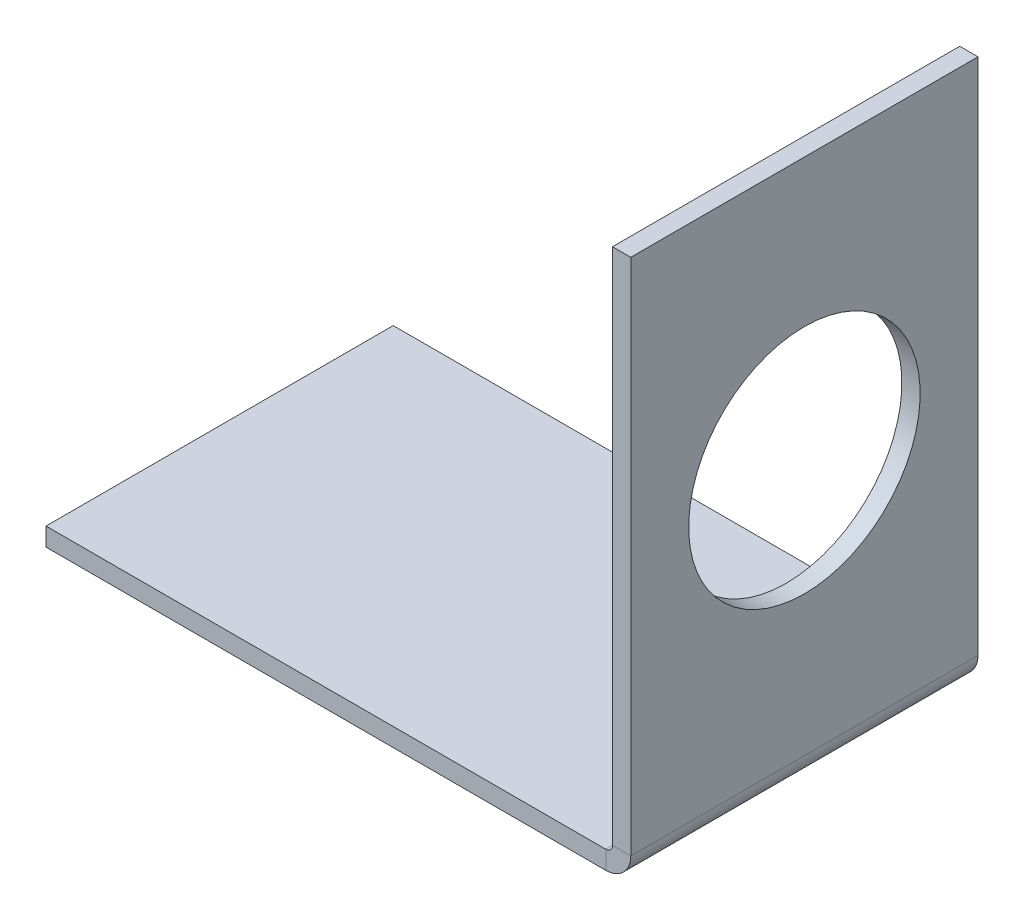
SolidWorks part; units mm, degrees
note: The reader was unsure of these and kept them because the rebuilt part matched: flange length of "邊線-凸緣1".
ref_plane "前基準面" through (0, 0, 0) normal (0, 0, 1) x (1, 0, 0)
ref_plane "上基準面" through (0, 0, 0) normal (0, 1, 0) x (1, 0, 0)
ref_plane "右基準面" through (0, 0, 0) normal (1, 0, 0) x (0, 0, -1)
sketch "草圖1" plane through (0, 0, 0) normal (0, 1, 0) x (1, 0, 0)
  line L1 (-31, 19) -> (31, 19)
  line L2 (-31, 19) -> (-31, -19)
  line L3 (-31, -19) -> (31, -19)
  line L4 (31, 19) -> (31, -19)
  line L5 (-31, 19) -> (31, -19) construction
  line L6 (-31, -19) -> (31, 19) construction
  point P0 (0, 0)
  dimension "D1" = 62
  dimension "D2" = 38
sheet metal parameters "鈑金1" thickness 2 parameters "D1"=0.7366, "厚度"=2
base flange "基材-凸緣1" sketch "草圖1" thickness 2 reverse thickness direction yes parameters "D1"=0.7366
edge flange "邊線-凸緣1" sketch "草圖5" flange angle 90 flange length 57.4732 flange position material outside bend radius 0.7366 thickness 2 relief rectangular parameters "D6"=10
sketch "草圖5" plane through (31, 2, 0) normal (1, 0, 0) x (0, 0, -1)
  line L0 (-19, 0) -> (19, 0) construction
  line L1 (-19, 0) -> (19, 0)
  line L2 (-19, 0) -> (-19, 57.4732)
  line L3 (-19, 57.4732) -> (19, 57.4732)
  line L4 (19, 57.4732) -> (19, 0)
  line L5 (19, 28.7366) -> (-19, 28.7366) construction
  line L7 (19, 0.7366) -> (-19, 0.7366) construction
  circle A0 centre (0, 28.7366) radius 12.6683
  dimension "D1" = 28
bend "邊線彎折1" bend radius 0.7366 bend angle 90 parameters "D5"=1
flat pattern "平板-型式1" [suppressed]
sketch "彎折-線1" plane through (0, 0, 0) normal (0, 1, 0) x (-1, 0, 0)
bend of the flat pattern "平板-<邊線彎折1>1"
